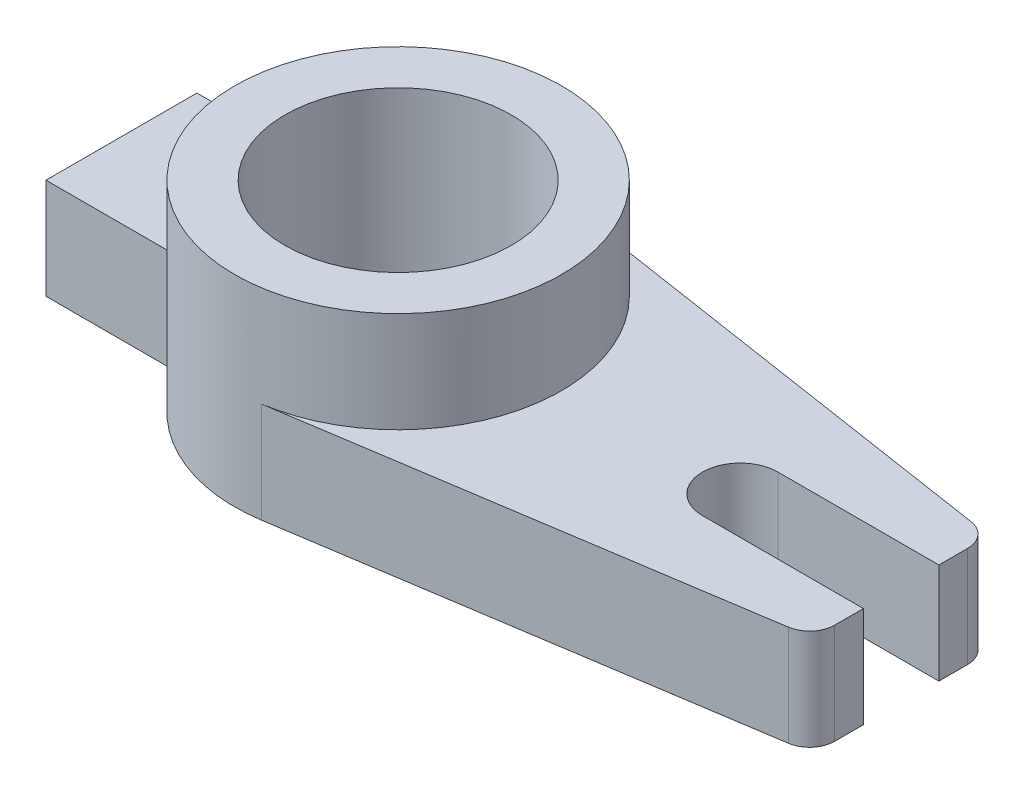
SolidWorks part; units mm, degrees
ref_plane "Front Plane" through (0, 0, 0) normal (0, 0, 1) x (1, 0, 0)
ref_plane "Top Plane" through (0, 0, 0) normal (0, 1, 0) x (1, 0, 0)
ref_plane "Right Plane" through (0, 0, 0) normal (1, 0, 0) x (0, 0, -1)
sketch "Sketch1" plane through (0, 0, 0) normal (0, 1, 0) x (1, 0, 0)
  line L0 (-28.8314, -15) -> (-55, -15)
  line L1 (-55, -15) -> (-55, 15)
  line L2 (-55, 15) -> (-28.8314, 15)
  line L3 (-55, 0) -> (55, 0) construction
  line L4 (95.7602, 18.1522) -> (4.9411, 32.1222)
  line L5 (100, 13.2103) -> (100, 7.5)
  line L6 (100, 7.5) -> (68, 7.5)
  line L7 (100, -7.5) -> (68, -7.5)
  line L8 (100, -13.2103) -> (100, -7.5)
  line L9 (95.7602, -18.1522) -> (4.9411, -32.1222)
  circle A0 centre (0, 0) radius 32.5
  arc A1 (68, 7.5) -> (68, -7.5) centre (68, 0) ccw
  arc A2 (95.7602, -18.1522) -> (100, -13.2103) centre (95, -13.2103) ccw
  arc A3 (100, 13.2103) -> (95.7602, 18.1522) centre (95, 13.2103) ccw
  circle A4 centre (0, 0) radius 22.5
  point P23 (100, -17.5)
  point P26 (100, 17.5)
  dimension "D1" = 65
  dimension "D8" = 32
  dimension "D9" = 5
  dimension "D10" = 45
  dimension "D2" = 30
  dimension "D3" = 15
  dimension "D4" = 55
  dimension "D5" = 100
  dimension "D6" = 35
  dimension "D7" = 15
extrude "Boss-Extrude1" add sketch "Sketch1" along normal blind 20 contours A0 L2 L1 L0 | A0 A4 | L5 A3 L4 A0 L9 A2 L8 L7 A1 L6 region at (-43.1283, 0, 0) region at (-31.5808, 0, 0) region at (55.8895, 0, 0)
extrude "Boss-Extrude2" add sketch "Sketch1<3>" along normal blind 40 contours A0 A4 region at (-31.5808, 0, 0)
sketch "Sketch1<3>" plane through (0, 0, 0) normal (0, 1, 0) x (1, 0, 0) same geometry as "Sketch1"
